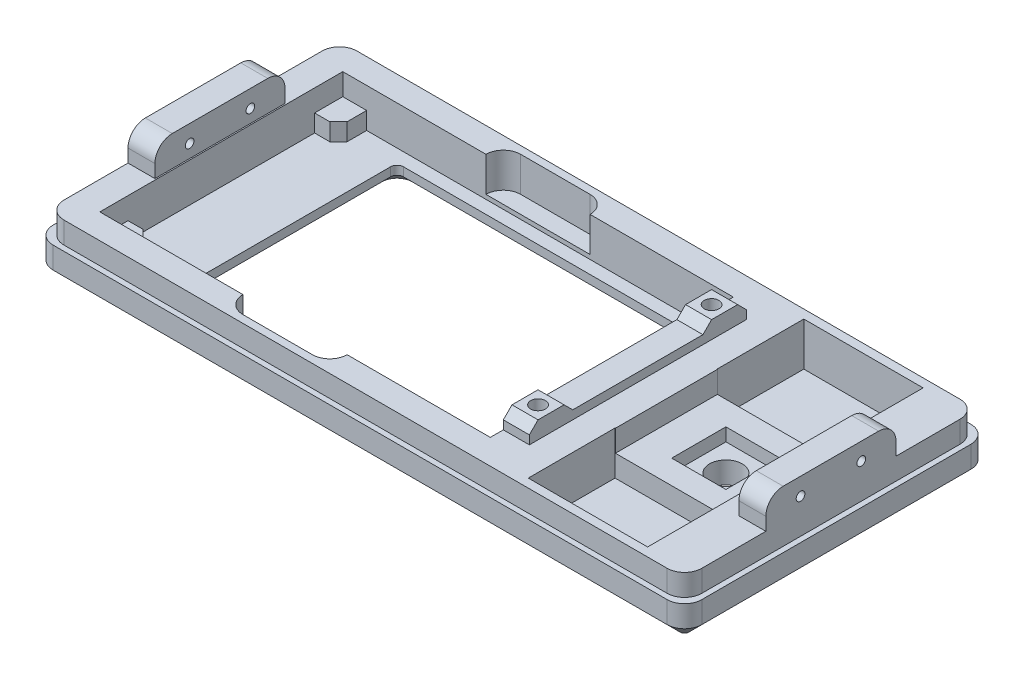
SolidWorks part; units mm, degrees
ref_plane "Front Plane" through (0, 0, 0) normal (0, 0, 1) x (1, 0, 0)
ref_plane "Top Plane" through (0, 0, 0) normal (0, 1, 0) x (1, 0, 0)
ref_plane "Right Plane" through (0, 0, 0) normal (1, 0, 0) x (0, 0, -1)
sketch "Sketch1" plane through (0, 0, 0) normal (0, 1, 0) x (1, 0, 0)
  line L1 (-74.75, 35) -> (74.75, 35)
  line L2 (-74.75, 35) -> (-74.75, -35)
  line L3 (-74.75, -35) -> (74.75, -35)
  line L4 (74.75, 35) -> (74.75, -35)
  line L5 (-74.75, 35) -> (74.75, -35) construction
  line L6 (-74.75, -35) -> (74.75, 35) construction
  point P0 (0, 0)
  dimension "D1" = 70
  dimension "D2" = 149.5
extrude "Boss-Extrude1" add sketch "Sketch1" along normal blind 8
fillet "Fillet1" radius 4 4 edges at (-74.75, 4, -35) (-74.75, 4, 35) (74.75, 4, -35) (74.75, 4, 35)
sketch "Sketch6" plane through (0, 8, 0) normal (0, 1, 0) x (1, 0, 0)
  line L1 (-73.5, 33.75) -> (73.5, 33.75)
  line L2 (-73.5, 33.75) -> (-73.5, -33.75)
  line L3 (-73.5, -33.75) -> (73.5, -33.75)
  line L4 (73.5, 33.75) -> (73.5, -33.75)
  line L5 (-73.5, 33.75) -> (73.5, -33.75) construction
  line L6 (-73.5, -33.75) -> (73.5, 33.75) construction
  point P0 (0, 0)
  dimension "D1" = 67.5
  dimension "D2" = 147
extrude "Boss-Extrude3" add sketch "Sketch6" along normal blind 5
fillet "Fillet2" radius 4 4 edges at (-73.5, 10.5, 33.75) (73.5, 10.5, 33.75) (73.5, 10.5, -33.75) (-73.5, 10.5, -33.75)
sketch "Sketch7" plane through (0, 13, 0) normal (0, 1, 0) x (1, 0, 0)
  line L0 (-73.5, 0) -> (0, 0) construction
  line L1 (-73.5, 29.75) -> (-73.5, -29.75) construction
  line L2 (0, 0) -> (0, 33.75) construction
  line L3 (69.5, 33.75) -> (-69.5, 33.75) construction
  line L4 (-73.5, -15) -> (-73.5, 15)
  line L5 (-73.5, 29.75) -> (-73.5, -29.75) construction
  line L6 (-73.5, 15) -> (-67.2945, 15)
  line L7 (-67.2945, 15) -> (-67.2945, -15)
  line L8 (-73.5, -15) -> (-67.2945, -15)
  line L9 (73.5, 15) -> (67.2945, 15)
  line L10 (73.5, -15) -> (73.5, 15)
  line L11 (73.5, -15) -> (67.2945, -15)
  line L12 (67.2945, 15) -> (67.2945, -15)
  point P14 (-67.2945, 0)
  dimension "D1" = 15
extrude "Boss-Extrude4" add sketch "Sketch7" along normal blind 7
sketch "Sketch8" plane through (-73.5, 0, 0) normal (-1, 0, 0) x (0, 0, 1)
  line L0 (0, 20) -> (0, 0) construction
  line L1 (-15, 20) -> (15, 20) construction
  circle A0 centre (-7, 16) radius 1
  circle A1 centre (7, 16) radius 1
  dimension "D1" = 2
  dimension "D2" = 4
  dimension "D3" = 14
extrude "Cut-Extrude3" cut sketch "Sketch8" against normal through all
fillet "Fillet5" radius 4 4 edges at (70.3973, 20, 15) (70.3973, 20, -15) (-70.3973, 20, 15) (-70.3973, 20, -15)
sketch "Sketch9" plane through (0, 13, 0) normal (0, 1, 0) x (1, 0, 0)
  line L0 (0, 0) -> (-67.2945, 0) construction
  line L1 (-67.2945, -15) -> (-67.2945, 15) construction
  line L3 (-67, 28) -> (23, 28)
  line L4 (-67, 28) -> (-67, -28)
  line L5 (-67, -28) -> (23, -28)
  line L6 (23, 28) -> (23, -28)
  line L7 (-67, 28) -> (23, -28) construction
  line L8 (-67, -28) -> (23, 28) construction
  point P5 (-22, 0)
  dimension "D1" = 90
  dimension "D2" = 56
  dimension "D3" = 22
extrude "Cut-Extrude4" cut sketch "Sketch9" against normal blind 5
sketch "Sketch10" plane through (0, 8, 0) normal (0, 1, 0) x (1, 0, 0)
  line L0 (-67, 28) -> (23, -28) construction
  line L1 (23, 28) -> (-67, -28) construction
  line L3 (-61.5, 28) -> (17.5, 28)
  line L4 (-61.5, 28) -> (-61.5, -28)
  line L5 (-61.5, -28) -> (17.5, -28)
  line L6 (17.5, 28) -> (17.5, -28)
  line L7 (-61.5, 28) -> (17.5, -28) construction
  line L8 (-61.5, -28) -> (17.5, 28) construction
  point P8 (-22, 0)
  dimension "D1" = 79
  dimension "D2" = 56
extrude "Cut-Extrude5" cut sketch "Sketch10" against normal blind 4
sketch "Sketch11" plane through (0, 4, 0) normal (0, 1, 0) x (1, 0, 0)
  line L0 (-61.5, 0) -> (17.5, 0) construction
  line L1 (-61.5, 28) -> (-61.5, -28) construction
  line L2 (17.5, -28) -> (17.5, 28) construction
  line L4 (-51.5, 25) -> (14.5, 25)
  line L5 (-51.5, 25) -> (-51.5, -25)
  line L6 (-51.5, -25) -> (14.5, -25)
  line L7 (14.5, 25) -> (14.5, -25)
  line L8 (-51.5, 25) -> (14.5, -25) construction
  line L9 (-51.5, -25) -> (14.5, 25) construction
  point P6 (-18.5, 0)
  dimension "D1" = 66
  dimension "D2" = 50
  dimension "D3" = 3
extrude "Cut-Extrude6" cut sketch "Sketch11" against normal through all
sketch "Sketch13" plane through (0, 13, 0) normal (0, 1, 0) x (1, 0, 0)
  line L0 (23, 0) -> (67.2945, 0) construction
  line L1 (23, -28) -> (23, 28) construction
  line L2 (67.2945, 11) -> (67.2945, -11) construction
  line L3 (23, -25) -> (23, 25)
  line L4 (23, 25) -> (29, 25)
  line L5 (29, 25) -> (29, -25)
  line L6 (23, -25) -> (29, -25)
  point P10 (29, 0)
  dimension "D1" = 25
  dimension "D2" = 6
extrude "Boss-Extrude5" add sketch "Sketch13" along normal blind 4
sketch "Sketch14" plane through (0, 17, 0) normal (0, 1, 0) x (1, 0, 0)
  line L0 (23, 0) -> (29, 0) construction
  line L1 (23, 25) -> (23, -25) construction
  line L2 (29, -25) -> (29, 25) construction
  circle A0 centre (26, 20) radius 1.6928
  circle A1 centre (26, -20) radius 1.6928
  dimension "D1" = 3
  dimension "D2" = 20
extrude "Cut-Extrude7" cut sketch "Sketch14" against normal through all
sketch "Sketch15" plane through (0, 17, 0) normal (0, 1, 0) x (1, 0, 0)
  line L0 (23, 0) -> (29, 0) construction
  line L1 (23, 25) -> (23, -25) construction
  line L2 (29, -25) -> (29, 25) construction
  line L3 (23, -15) -> (23, 15)
  line L4 (23, -28) -> (23, 28) construction
  line L5 (23, 15) -> (29, 15)
  line L6 (29, -25) -> (29, 25) construction
  line L7 (29, 15) -> (29, -15)
  line L8 (23, -15) -> (29, -15)
  dimension "D1" = 15
extrude "Cut-Extrude8" cut sketch "Sketch15" against normal blind 2
chamfer "Chamfer2" distance 2 angle 45 2 edges at (26, 0, 18.3072) (26, 0, -18.3072)
sketch "Sketch16" plane through (0, 13, 0) normal (0, 1, 0) x (1, 0, 0)
  line L0 (0, 0) -> (67.2945, 0) construction
  line L1 (67.2945, 11) -> (67.2945, -11) construction
  circle A0 centre (49.2945, 0) radius 3.75
  dimension "D1" = 7.5
  dimension "D2" = 18
extrude "Cut-Extrude9" cut sketch "Sketch16" against normal through all
sketch "Sketch17" plane through (0, 13, 0) normal (0, 1, 0) x (1, 0, 0)
  line L1 (43.0445, 6.25) -> (55.5445, 6.25)
  line L2 (43.0445, 6.25) -> (43.0445, -6.25)
  line L3 (43.0445, -6.25) -> (55.5445, -6.25)
  line L4 (55.5445, 6.25) -> (55.5445, -6.25)
  line L5 (43.0445, 6.25) -> (55.5445, -6.25) construction
  line L6 (43.0445, -6.25) -> (55.5445, 6.25) construction
  point P0 (49.2945, 0)
  dimension "D1" = 12.5
  dimension "D2" = 12.5
extrude "Cut-Extrude10" cut sketch "Sketch17" against normal blind 8
sketch "Sketch20" plane through (0, 13, 0) normal (0, 1, 0) x (1, 0, 0)
  line L0 (-67.2945, 0) -> (67.2945, 0) construction
  line L1 (-67.2945, -11) -> (-67.2945, 11) construction
  line L2 (67.2945, 11) -> (67.2945, -11) construction
  line L3 (-22, 28) -> (-22, 33.75) construction
  line L4 (23, 28) -> (-67, 28) construction
  line L5 (69.5, 33.75) -> (-69.5, 33.75) construction
  line L6 (-10, 28) -> (-34, 28)
  line L7 (-34, 28) -> (-34, 32)
  line L8 (-34, 32) -> (-10, 32)
  line L9 (-10, 28) -> (-10, 32)
  line L10 (-10, -28) -> (-10, -32)
  line L11 (-34, -32) -> (-10, -32)
  line L12 (-34, -28) -> (-34, -32)
  line L13 (-10, -28) -> (-34, -28)
  point P17 (-22, 32)
  dimension "D1" = 12
  dimension "D2" = 4
extrude "Cut-Extrude12" cut sketch "Sketch20" against normal blind 8
fillet "Fillet6" radius 4 4 edges at (-34, 9, 32) (-10, 9, 32) (-10, 9, -32) (-34, 9, -32)
chamfer "Chamfer3" distance 2 angle 45 4 edges at (26, 17, 15) (26, 17, -15) (26, 17, -25) (26, 17, 25)
sketch "Sketch23" plane through (0, 8, 0) normal (0, 1, 0) x (1, 0, 0)
  line L0 (-61.5, 0) -> (-67, 0) construction
  line L1 (-61.5, 28) -> (-61.5, -28) construction
  line L2 (-67, 28) -> (-67, -28) construction
  line L3 (-61.5, -21.5) -> (-61.5, 21.5)
  line L4 (-61.5, 28) -> (-61.5, -28) construction
  line L5 (-61.5, 21.5) -> (-67, 21.5)
  line L6 (-67, 21.5) -> (-67, -21.5)
  line L7 (-61.5, -21.5) -> (-67, -21.5)
  line L8 (-22, -28) -> (-22, -10.1702) construction
  line L9 (-10, -28) -> (-34, -28) construction
  line L10 (17.5, 21.5) -> (23, 21.5)
  line L11 (17.5, -21.5) -> (17.5, 21.5)
  line L12 (17.5, -21.5) -> (23, -21.5)
  line L13 (23, 21.5) -> (23, -21.5)
  point P12 (-67, 0)
  dimension "D1" = 21.5
  dimension "D2" = 5.5
extrude "Cut-Extrude15" cut sketch "Sketch23" against normal blind 4
fillet "Fillet7" radius 1.5 4 edges at (14.5, 2, -25) (14.5, 2, 25) (-51.5, 2, 25) (-51.5, 2, -25)
chamfer "Chamfer6" distance 2 angle 45 4 edges at (-61.5, 6, 21.5) (-61.5, 6, -21.5) (17.5, 6, 21.5) (17.5, 6, -21.5)
sketch "Sketch26" plane through (0, 13, 0) normal (0, 1, 0) x (1, 0, 0)
  line L0 (-69.5, -33.75) -> (69.5, -33.75) construction
  line L1 (35.5, -11.75) -> (63, -11.75)
  line L2 (35.5, -11.75) -> (35.5, -31.75)
  line L3 (35.5, -31.75) -> (63, -31.75)
  line L4 (63, -11.75) -> (63, -31.75)
  line L5 (35.5, -11.75) -> (63, -31.75) construction
  line L6 (35.5, -31.75) -> (63, -11.75) construction
  line L7 (73.5, -29.75) -> (73.5, -15) construction
  line L8 (0, 0) -> (16.2431, 0) construction
  line L9 (35.5, 31.75) -> (63, 31.75)
  line L10 (63, 11.75) -> (63, 31.75)
  line L11 (35.5, 11.75) -> (63, 11.75)
  line L12 (35.5, 11.75) -> (35.5, 31.75)
  point P0 (49.25, -21.75)
  dimension "D1" = 20
  dimension "D2" = 27.5
  dimension "D3" = 12
  dimension "D4" = 10.5
extrude "Cut-Extrude16" cut sketch "Sketch26" against normal blind 10
sketch "Sketch27" plane through (0, 13, 0) normal (0, 1, 0) x (1, 0, 0)
  line L0 (63, -31.75) -> (63, -11.75) construction
  line L1 (35.5891, 14.4188) -> (63, 14.4188)
  line L2 (35.5891, 14.4188) -> (35.5891, -14.4188)
  line L3 (35.5891, -14.4188) -> (63, -14.4188)
  line L4 (63, 14.4188) -> (63, -14.4188)
  line L5 (35.5891, 14.4188) -> (63, -14.4188) construction
  line L6 (35.5891, -14.4188) -> (63, 14.4188) construction
  point P0 (49.2945, 0)
extrude "Cut-Extrude17" cut sketch "Sketch27" against normal blind 5
chamfer "Chamfer7" distance 3 angle 45 8 edges at (0, 0, 35) (73.5784, 0, 33.8284) (-73.5784, 0, 33.8284) (74.75, 0, 0) (-74.75, 0, 0) (73.5784, 0, -33.8284) (-73.5784, 0, -33.8284) (0, 0, -35)
chamfer "Chamfer8" distance 2 angle 45 8 edges at (14.5, 0, 0) (14.0607, 0, -24.5607) (14.0607, 0, 24.5607) (-18.5, 0, -25) (-18.5, 0, 25) (-51.0607, 0, -24.5607) (-51.0607, 0, 24.5607) (-51.5, 0, 0)
